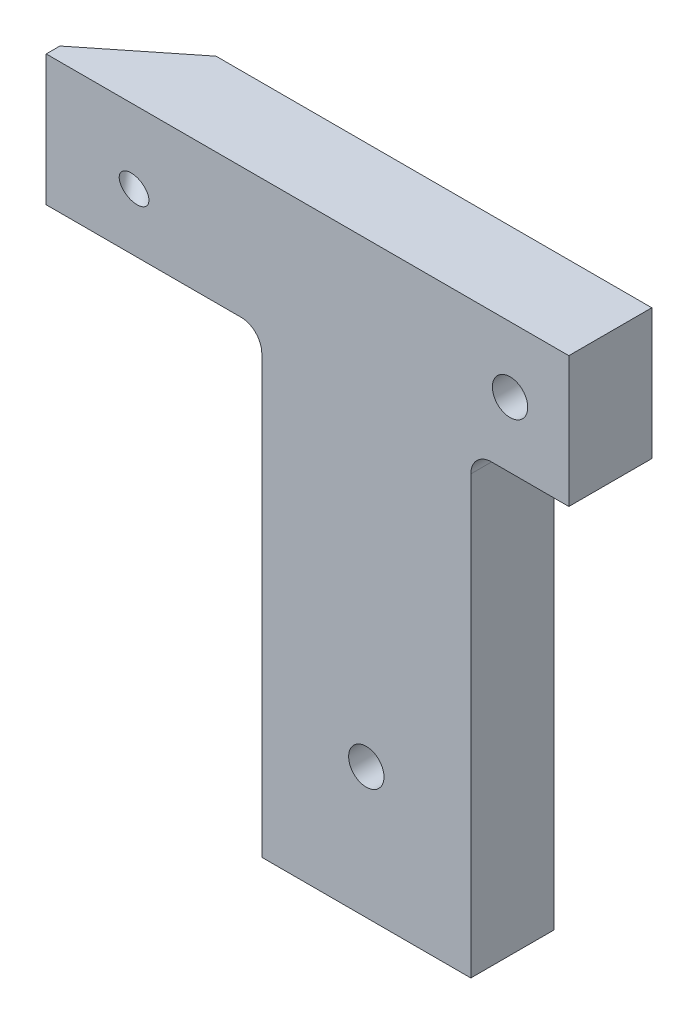
SolidWorks part; units mm, degrees
other "Markup1"
sketch "Sketch12" plane through (40, 0, 0) normal (0.1663, -0.0186, -0.9859) x (0.442, -0.8924, 0.0914)
material "6061-T4 (SS)"
ref_plane "Front Plane" through (0, 0, 0) normal (0, 0, 1) x (1, 0, 0)
ref_plane "Top Plane" through (0, 0, 0) normal (0, 1, 0) x (1, 0, 0)
ref_plane "Right Plane" through (0, 0, 0) normal (1, 0, 0) x (0, 0, -1)
sketch "Sketch1" plane through (0, 0, 0) normal (0, 0, 1) x (1, 0, 0)
  line L1 (0, 0) -> (40, 0)
  line L2 (0, 0) -> (0, 45)
  line L3 (0, 45) -> (40, 45)
  line L4 (40, 0) -> (40, 45)
  dimension "D1" = 40
  dimension "D2" = 45
extrude "Boss-Extrude1" add sketch "Sketch1" along normal blind 6.35
ref_plane "Plane1" through (-7.1054, 3.0997, -8.9102) normal (-0.6016, 0.2625, -0.7544) x (-0.7988, -0.1977, 0.5682)
sketch "Sketch4" plane through (-7.1054, 3.0997, -8.9102) normal (-0.6016, 0.2625, -0.7544) x (-0.7988, -0.1977, 0.5682)
  line L5 (1.1047, 52.5016) -> (-18.8953, 52.5016)
  line L6 (1.1047, 52.5016) -> (1.1047, 32.5016)
  line L7 (1.1047, 32.5016) -> (-18.8953, 32.5016)
  line L8 (-18.8953, 52.5016) -> (-18.8953, 32.5016)
  line L9 (1.1047, 52.5016) -> (-18.8953, 32.5016) construction
  line L10 (1.1047, 32.5016) -> (-18.8953, 52.5016) construction
  point P0 (-8.8953, 42.5016)
  dimension "D1" = 20
extrude "Cut-Extrude1" cut sketch "Sketch4" against normal blind 4 contours L8 L7 L6 L5
sketch "Sketch7" plane through (0, 0, 0) normal (0, 0, -1) x (-1, 0, 0)
  line L1 (0, 0) -> (-16.5, 0)
  line L2 (0, 0) -> (0, 35)
  line L3 (0, 35) -> (-14.9125, 35)
  line L4 (-16.5, 0) -> (-16.5, 33.4125)
  line L5 (0, 0) -> (-40, 0) construction
  line L6 (-40, 0) -> (-32.5, 0)
  line L7 (-40, 0) -> (-40, 35)
  line L8 (-40, 35) -> (-34.0875, 35)
  line L9 (-32.5, 0) -> (-32.5, 33.4125)
  line L11 (-40, 0) -> (-40, 45) construction
  line L13 (-32.5, -28) -> (-32.5, 21.4125) construction
  line L14 (-16.5, -28) -> (-16.5, 18.8194) construction
  arc A0 (-14.9125, 35) -> (-16.5, 33.4125) centre (-14.9125, 33.4125) ccw
  arc A1 (-34.0875, 35) -> (-32.5, 33.4125) centre (-34.0875, 33.4125) cw
  point P9 (-16.5, 35)
  dimension "D2" = 1.5875
  dimension "D3" = 1.5875
  dimension "D1" = 35
extrude "Cut-Extrude2" cut sketch "Sketch7" against normal blind 19
hole_wizard "#2-56 Tapped Hole1" positions "Sketch8" profile "Sketch9" tap size "#2-56" standard "ANSI Inch" end condition through all
sketch "Sketch8" plane through (-4.699, 2.0499, -5.8925) normal (-0.6016, 0.2625, -0.7544) x (-0.7988, -0.1977, 0.5682)
  point P0 (-9.5556, 39.3183)
  point P5 (0, 0)
sketch "Sketch9" plane through (2.9339, 41.0742, 1.5966) normal (0.6739, 0.6739, -0.3029) x (-0.4289, 0.6907, 0.5823)
  line L0 (0, 0) -> (0, 36.666)
  line L1 (0, 36.666) -> (0.889, 36.666)
  line L2 (0.889, 36.666) -> (0.889, 0)
  line L5 (0.889, 0) -> (0, 0)
  line L11 (0, -6.35) -> (0, 107.95) construction
  dimension "Thru Tap Drill Dia." = 1.778
  dimension "Thru Tap Drill Depth" = 36.666
cosmetic thread "Hole Thread2" parameters "D2"=2.1844
hole_wizard "CBORE for #2 Socket Head Cap Screw1" positions "Sketch10" profile "Sketch11" counterbore size "#2" standard "ANSI Inch" end condition through all
sketch "Sketch10" plane through (0, 0, 0) normal (0, 0, -1) x (-1, 0, 0)
  point P0 (-24.5, 10)
  point P7 (-35.5, 40)
  point P14 (0, 0)
  point P15 (0, 0)
  point P16 (-35.5, 40)
  point P18 (-24.5, 10)
sketch "Sketch11" plane through (24.5, 10, 0) normal (1, 0, 0) x (0, 1, 0)
  line L0 (0, 0) -> (0, 6.35)
  line L1 (0, 6.35) -> (1.3525, 6.35)
  line L3 (1.3525, 6.35) -> (1.3525, 2.1844)
  line L4 (1.3525, 2.1844) -> (2.3812, 2.1844)
  line L5 (2.3812, 2.1844) -> (2.3812, 0)
  line L7 (2.3812, 0) -> (0, 0)
  line L11 (0, -6.35) -> (0, 107.95) construction
  dimension "Thru Hole Dia." = 2.7051
  dimension "Thru Hole Depth" = 6.35
  dimension "C'Bore Dia." = 4.7625
  dimension "C'Bore Depth" = 2.1844
